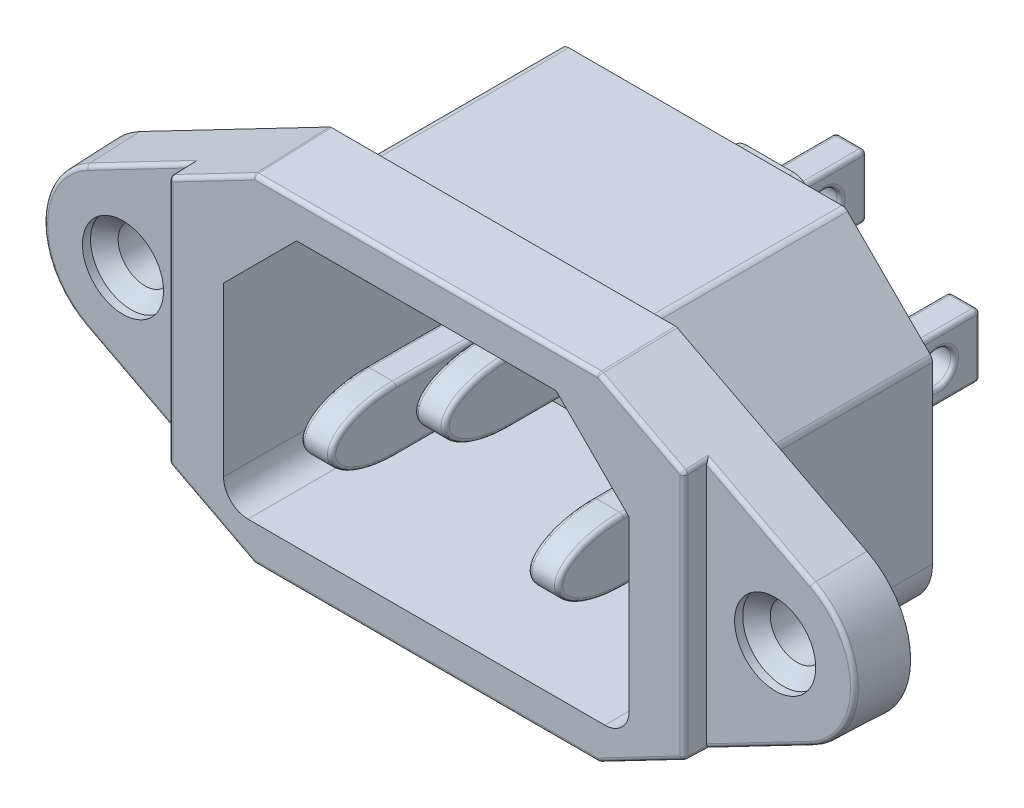
SolidWorks part; units mm, degrees
ref_plane "Alzado XY" through (0, 0, 0) normal (0, 0, 1) x (1, 0, 0)
ref_plane "Planta XZ" through (0, 0, 0) normal (0, 1, 0) x (1, 0, 0)
ref_plane "Vista lateral YZ" through (0, 0, 0) normal (1, 0, 0) x (0, 0, -1)
sketch "Croquis1" plane through (0, 0, 0) normal (0, 0, 1) x (1, 0, 0)
  line L0 (-12.5, 3.675) -> (-12.5, -8.175)
  line L1 (-12.5, -8.175) -> (12.5, -8.175)
  line L2 (12.5, -8.175) -> (12.5, 3.675)
  line L3 (12.5, 3.675) -> (8, 8.175)
  line L4 (8, 8.175) -> (-8, 8.175)
  line L5 (-8, 8.175) -> (-12.5, 3.675)
  line L6 (-22.4087, -4.4351) -> (-10.662, -10.55)
  line L7 (-6.05, -4.45) -> (-7.95, -4.45)
  line L8 (-6.05, -4.45) -> (-6.05, -0.55)
  line L9 (-6.05, -0.55) -> (-7.95, -0.55)
  line L10 (-7.95, -4.45) -> (-7.95, -0.55)
  line L11 (-6.05, -4.45) -> (-7.95, -0.55) construction
  line L12 (-6.05, -0.55) -> (-7.95, -4.45) construction
  line L13 (0.95, 0.55) -> (-0.95, 0.55)
  line L14 (0.95, 0.55) -> (0.95, 4.45)
  line L15 (0.95, 4.45) -> (-0.95, 4.45)
  line L16 (-0.95, 0.55) -> (-0.95, 4.45)
  line L17 (0.95, 0.55) -> (-0.95, 4.45) construction
  line L18 (0.95, 4.45) -> (-0.95, 0.55) construction
  line L19 (7.95, -4.45) -> (6.05, -4.45)
  line L20 (7.95, -4.45) -> (7.95, -0.55)
  line L21 (7.95, -0.55) -> (6.05, -0.55)
  line L22 (6.05, -4.45) -> (6.05, -0.55)
  line L23 (7.95, -4.45) -> (6.05, -0.55) construction
  line L24 (7.95, -0.55) -> (6.05, -4.45) construction
  line L25 (-10.662, -10.55) -> (10.662, -10.55)
  line L26 (10.662, -10.55) -> (22.4087, -4.4351)
  line L27 (22.4087, 4.4351) -> (10.662, 10.55)
  line L28 (10.662, 10.55) -> (-10.662, 10.55)
  line L29 (-10.662, 10.55) -> (-22.4087, 4.4351)
  line L30 (-7, -2.5) -> (7, -2.5) construction
  line L31 (0, 2.5) -> (0, -2.5) construction
  line L32 (-20.1, 0) -> (20.1, 0) construction
  line L33 (0, 8.175) -> (0, -8.175) construction
  circle A0 centre (20.1, 0) radius 2.5
  circle A1 centre (-20.1, 0) radius 2.5
  circle A2 centre (20.1, 0) radius 1.65
  circle A3 centre (-20.1, 0) radius 1.65
  arc A4 (22.4087, 4.4351) -> (22.4087, -4.4351) centre (20.1, 0) cw
  arc A5 (-22.4087, -4.4351) -> (-22.4087, 4.4351) centre (-20.1, 0) cw
  point P3 (-7, -2.5)
  point P11 (0, 2.5)
  point P16 (7, -2.5)
  point P21 (0, 0)
  point P25 (0, 10.55)
  point P40 (0, 0)
  point P47 (0, -10.55)
  point P52 (0, 0)
  point P53 (0, -2.5)
  dimension "D7" = 5
  dimension "D8" = 3.3
  dimension "D9" = 5
  dimension "D10" = 40.2
  dimension "D1" = 16.35
  dimension "D2" = 3.9
  dimension "D3" = 1.9
  dimension "D4" = 5
  dimension "D5" = 14
  dimension "D6" = 25
  dimension "D11" = 21.1
  dimension "D12" = 55
  dimension "D13" = 45
  dimension "D14" = 4.5
extrude "Extruir-Lámina1" add sketch "Croquis1" against normal blind 17.2 thin contours L5 L0 L1 L2 L3 L4 thin type one direction wall 1.5
sketch "Croquis2" plane through (0, 0, -17.2) normal (0, 0, -1) x (-1, 0, 0)
  line L0 (14, -9.675) -> (-14, -9.675) construction
  line L1 (14, 4.2963) -> (14, -9.675) construction
  line L2 (8.6213, 9.675) -> (14, 4.2963) construction
  line L3 (-8.6213, 9.675) -> (8.6213, 9.675) construction
  line L4 (-14, 4.2963) -> (-8.6213, 9.675) construction
  line L5 (-14, -9.675) -> (-14, 4.2963) construction
  line L6 (14, -9.675) -> (-14, -9.675)
  line L7 (14, 4.2963) -> (14, -9.675)
  line L8 (8.6213, 9.675) -> (14, 4.2963)
  line L9 (-8.6213, 9.675) -> (8.6213, 9.675)
  line L10 (-14, 4.2963) -> (-8.6213, 9.675)
  line L11 (-14, -9.675) -> (-14, 4.2963)
extrude "Saliente-Extruir1" add sketch "Croquis2" against normal blind 1.5
extrude "Cortar-Extruir1" cut sketch "Croquis1<4>" against normal through all contours L10 L7 L8 L9 | L22 L19 L20 L21 | L16 L13 L14 L15 region at (-7, -2.5, 0) region at (0, 2.5, 0) region at (7, -2.5, 0)
sketch "Croquis1<4>" plane through (0, 0, 0) normal (0, 0, 1) x (1, 0, 0) same geometry as "Croquis1"
sketch "Croquis3" plane through (0, 0, -17.2) normal (0, 0, -1) x (-1, 0, 0)
  line L0 (6.05, -4.45) -> (7.95, -4.45) construction
  line L1 (7.95, -4.45) -> (7.95, -0.55) construction
  line L2 (6.05, -0.55) -> (7.95, -0.55) construction
  line L3 (6.05, -4.45) -> (6.05, -0.55) construction
  line L4 (0.95, 0.55) -> (0.95, 4.45) construction
  line L5 (-0.95, 4.45) -> (0.95, 4.45) construction
  line L6 (-0.95, 0.55) -> (-0.95, 4.45) construction
  line L7 (-0.95, 0.55) -> (0.95, 0.55) construction
  line L8 (-7.95, -4.45) -> (-6.05, -4.45) construction
  line L9 (-6.05, -4.45) -> (-6.05, -0.55) construction
  line L10 (-7.95, -0.55) -> (-6.05, -0.55) construction
  line L11 (-7.95, -4.45) -> (-7.95, -0.55) construction
  line L12 (6.05, -4.45) -> (7.95, -4.45)
  line L13 (7.95, -4.45) -> (7.95, -0.55)
  line L14 (6.05, -0.55) -> (7.95, -0.55)
  line L15 (6.05, -4.45) -> (6.05, -0.55)
  line L16 (0.95, 0.55) -> (0.95, 4.45)
  line L17 (-0.95, 4.45) -> (0.95, 4.45)
  line L18 (-0.95, 0.55) -> (-0.95, 4.45)
  line L19 (-0.95, 0.55) -> (0.95, 0.55)
  line L20 (-7.95, -4.45) -> (-6.05, -4.45)
  line L21 (-6.05, -4.45) -> (-6.05, -0.55)
  line L22 (-7.95, -0.55) -> (-6.05, -0.55)
  line L23 (-7.95, -4.45) -> (-7.95, -0.55)
extrude "Extruir-Lámina2" add sketch "Croquis3" along normal blind 4 thin thin type one direction wall 1.5
fillet "Redondeo1" radius 3 2 edges at (-14, -9.675, -8.6) (14, -9.675, -8.6)
fillet "Redondeo2" radius 1.5 2 edges at (12.5, -8.175, -7.85) (-12.5, -8.175, -7.85)
extrude "Saliente-Extruir2" add sketch "Croquis1<5>" against normal blind 4.75 contours L4 L5 L0 L1 L2 L3 L7 L10 L9 L8 L13 L16 L15 L14 L19 L22 L21 L20 | L29 A5 L6 L25 L26 A4 L27 L28 region at (0, -0.3185, 0)
sketch "Croquis1<5>" plane through (0, 0, 0) normal (0, 0, 1) x (1, 0, 0) same geometry as "Croquis1"
draft "Ángulo de salida9" type of draft neutral plane draft angle 2 faces to draft 8 face at (-23.7544, 0, -2.375) face at (-16.5354, -7.4925, -2.375) face at (0, -10.55, -2.375) face at (16.5354, -7.4925, -2.375) face at (-16.5354, 7.4925, -2.375) face at (0, 10.55, -2.375) face at (23.7544, 0, -2.375) face at (16.5354, 7.4925, -2.375) neutral plane through (-20.1, 0, -4.75) neutral plane normal (0, 0, -1) reverse direction yes parameters "D1"=2
sketch "Croquis4" plane through (0, 0, 0) normal (0, 0, 1) x (1, 0, 0)
  line L1 (15.875, -10.55) -> (-15.875, -10.55)
  line L2 (15.875, -10.55) -> (15.875, 10.55)
  line L3 (15.875, 10.55) -> (-15.875, 10.55)
  line L4 (-15.875, -10.55) -> (-15.875, 10.55)
  line L5 (15.875, -10.55) -> (-15.875, 10.55) construction
  line L6 (15.875, 10.55) -> (-15.875, -10.55) construction
  line L7 (10.662, 10.55) -> (-10.662, 10.55) construction
  point P0 (0, 0)
  dimension "D1" = 31.75
extrude "Cortar-Extruir2" cut sketch "Croquis4" against normal blind 1.4 flip side to cut
hole_wizard "Avellanado para tornillo con cabeza plana avellanada de M31" positions "Croquis5" profile "Croquis7" countersink size "M3" standard "ISO" end condition up to next
sketch "Croquis5" plane through (0, 0, -1.4) normal (0, 0, 1) x (1, 0, 0)
  point P0 (-20.1, 0)
  point P3 (20.1, 0)
sketch "Croquis7" plane through (-20.1, 0, -1.4) normal (1, 0, 0) x (0, -1, 0)
  line L0 (0, 0) -> (0, 3.35)
  line L1 (0, 3.35) -> (1.65, 3.35)
  line L2 (1.65, 3.35) -> (1.65, 1.35)
  line L3 (1.65, 1.35) -> (2.5, 0.5)
  line L4 (2.5, 0.5) -> (2.5, 0)
  line L6 (2.5, 0) -> (0, 0)
  line L7 (-1.65, 1.35) -> (-2.5, 0.5) construction
  line L11 (0, -6.35) -> (0, 107.95) construction
  dimension "Diámetro de taladro hasta el siguiente" = 3.3
  dimension "Profundidad de taladro hasta el siguiente" = 3.35
  dimension "Diámetro de avellanado" = 5
  dimension "Ángulo de avellanado" = 90
  dimension "Espacio libre" = 0.5
fillet "Redondeo3" radius 0.25 22 edges at (-19.1149, -6.0179, -1.4) (-24.983, 0, -1.4) (19.1149, -6.0179, -1.4) (24.983, 0, -1.4) (15.875, 7.6769, -0.7) (13.2482, 9.0167, 0) (0, 10.3841, 0) (-13.2482, 9.0167, 0) (-15.875, 7.6769, -0.7) (-15.875, -7.6769, -0.7) (-15.875, 0, 0) (-13.2482, -9.0167, 0) (0, -10.3841, 0) (13.2482, -9.0167, 0) (15.875, 0, 0) (15.875, -7.6769, -0.7) (-10.6417, -10.4671, -2.375) (10.6417, -10.4671, -2.375) (10.6417, 10.4671, -2.375) (-10.6417, 10.4671, -2.375) (-19.1149, 6.0179, -1.4) (19.1149, 6.0179, -1.4)
fillet "Redondeo4" radius 1 12 edges at (-4.55, -5.95, -19.2) (-9.45, -5.95, -19.2) (-9.45, 0.95, -19.2) (-4.55, 0.95, -19.2) (-2.45, -0.95, -19.2) (-2.45, 5.95, -19.2) (2.45, 5.95, -19.2) (2.45, -0.95, -19.2) (4.55, -5.95, -19.2) (9.45, -5.95, -19.2) (9.45, 0.95, -19.2) (4.55, 0.95, -19.2)
fillet "Redondeo5" radius 0.5 4 edges at (14, 4.2963, -10.975) (8.6213, 9.675, -10.975) (-8.6213, 9.675, -10.975) (-14, 4.2963, -10.975)
sketch "Croquis8" plane through (0, 0, -17.2) normal (0, 0, -1) x (-1, 0, 0)
  line L0 (1, -8.675) -> (13, -8.675) construction
  line L1 (-3.9533, -3.2) -> (3.9533, -3.2) construction
  line L2 (12.5, -8.175) -> (-12.5, -8.175) construction
  line L4 (0, 8.175) -> (0, -8.175) construction
  line L5 (-3.9533, -6.2) -> (3.9533, -6.2) construction
  line L6 (-0.95, 0.55) -> (0.95, 0.55) construction
  line L7 (-2.2659, 6.45) -> (2.2659, 6.45) construction
  line L8 (4.7341, 1.45) -> (9.2659, 1.45) construction
  line L9 (-9.2659, 1.45) -> (-4.7341, 1.45) construction
  line L10 (-0.95, 4.45) -> (0.95, 4.45) construction
  line L11 (-7.95, -0.55) -> (-6.05, -0.55) construction
  text T0 "10A~15A" font "Arial" height 2
  text T1 "10A" font "Arial" height 2
  text T2 "250V" font "Arial" height 2
  text T3 "F" font "Arial" height 2
  text T4 "N" font "Arial" height 2
  text T5 "L" font "Arial" height 2
  point P7 (0, -6.2)
  point P9 (7, -8.675)
  point P17 (0, -3.2)
  point P24 (0, 6.45)
  point P27 (-7, 1.45)
  point P32 (7, 1.45)
  dimension "D1" = 0.5
  dimension "D2" = 12
  dimension "D3" = 3
  dimension "D4" = 3.75
  dimension "D5" = 2
  dimension "D6" = 2
extrude "Saliente-Extruir3" add sketch "Croquis8" along normal blind 0.2
sketch "Croquis10" plane through (0, 0, 0) normal (1, 0, 0) x (0, 0, -1)
  line L0 (26.2, 4.45) -> (26.2, 0.55)
  line L1 (26.2, 0.55) -> (4.2, 0.55)
  line L2 (4.2, 4.45) -> (26.2, 4.45)
  line L3 (4.2, 4.45) -> (4.2, 0.55) construction
  line L4 (21.2, 4.95) -> (21.2, 0.05) construction
  line L5 (26.2, 2.5) -> (4.2, 2.5) construction
  circle A0 centre (23.6, 2.5) radius 1
  ellipse E0 centre (4.2, 2.5) end of major axis (0.2, 2.5) minor radius 1.95 (4.2, 4.45) -> (4.2, 0.55) ccw
  dimension "D2" = 2
  dimension "D1" = 3.9
  dimension "D3" = 5
  dimension "D4" = 2.6
  dimension "D5" = 4
  dimension "D6" = 26
extrude "Saliente-Extruir4" add sketch "Croquis10" along normal mid plane 1.9 separate body contours A0 | L2 L0 L1 E0 region at (0, 2.5, -23.6)
fillet "Redondeo7" radius 0.25 12 edges at (-0.95, 2.5, -24.6) (-0.95, 0.55, -15.2) (-0.95, 2.5, -26.2) (-0.95, 4.45, -15.2) (-0.95, 2.5, -0.2) (0.95, 2.5, -24.6) (0.95, 4.45, -15.2) (0.95, 2.5, -26.2) (0.95, 0.55, -15.2) (0.95, 2.5, -0.2) (0, 4.45, -26.2) (0, 0.55, -26.2)
move or copy body "Sólido-Mover/Copiar1" bodies to move or copy 112 copy yes number of copies 1 translate (7, -5, 0)
move or copy body "Sólido-Mover/Copiar2" bodies to move or copy 112 copy yes number of copies 1 translate (-7, -5, 0)
sketch "Croquis11" plane through (0, 0, -26.2) normal (0, 0, -1) x (-1, 0, 0)
  point P0 (-7, -2.5)
  point P1 (0, 2.5)
  point P2 (7, -2.5)
other "PuntoC1" parameters "Diámetro"=2.5, "Longitud de terminal"=30
ref_axis "Eje1" through (0, 2.5, -36.2) along (0, 0, 1)
other "PuntoC2" parameters "Diámetro"=2.5, "Longitud de terminal"=30
ref_axis "Eje2" through (-7, -2.5, -36.2) along (0, 0, 1)
other "PuntoC3" parameters "Diámetro"=2.5, "Longitud de terminal"=30
ref_axis "Eje3" through (7, -2.5, -36.2) along (0, 0, 1)
